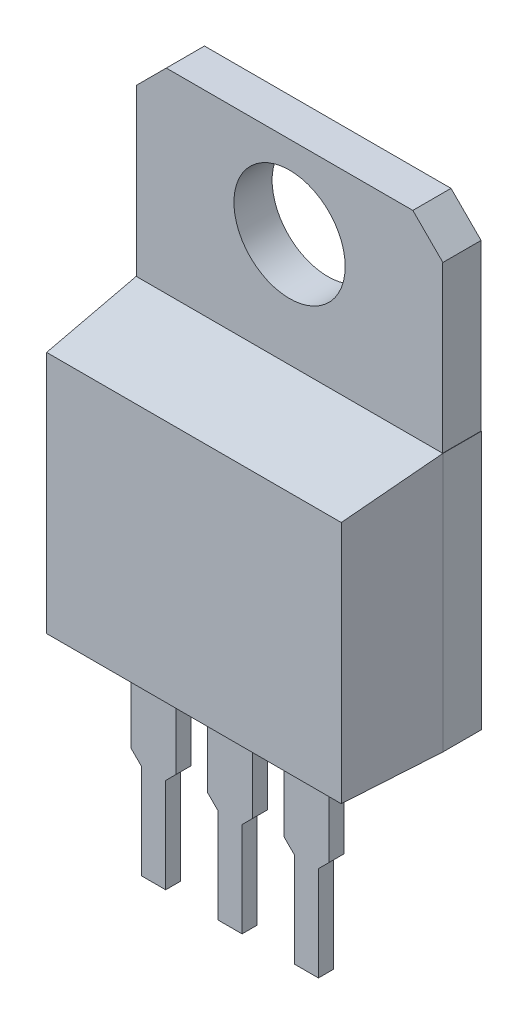
SolidWorks part; units mm, degrees
ref_plane "Plan de face" through (0, 0, 0) normal (0, 0, 1) x (1, 0, 0)
ref_plane "Plan de dessus" through (0, 0, 0) normal (0, 1, 0) x (1, 0, 0)
ref_plane "Plan de droite" through (0, 0, 0) normal (1, 0, 0) x (0, 0, -1)
sketch "Esquisse1" plane through (0, 0, 0) normal (0, 0, 1) x (1, 0, 0)
  line L0 (0, 15.1) -> (0, 12.36) construction
  line L1 (-5.1, 15.1) -> (5.1, 15.1)
  line L2 (-5.1, 15.1) -> (-5.1, 0)
  line L3 (-5.1, 0) -> (5.1, 0)
  line L4 (5.1, 15.1) -> (5.1, 0)
  line L5 (-5.1, 15.1) -> (5.1, 0) construction
  line L6 (-5.1, 0) -> (5.1, 15.1) construction
  circle A0 centre (0, 12.36) radius 1.85
  point P0 (0, 7.55)
  dimension "D4" = 3.7
  dimension "D1" = 15.1
  dimension "D2" = 10.2
  dimension "D3" = 2.74
extrude "Boss.-Extru.1" add sketch "Esquisse1" along normal blind 1.27
sketch "Esquisse2" plane through (0, 0, 1.27) normal (0, 0, 1) x (1, 0, 0)
  line L0 (5.1, 0) -> (5.1, 15.1) construction
  line L1 (-5.1, 0) -> (5.1, 0)
  line L2 (-5.1, 0) -> (-5.1, 8.6)
  line L3 (-5.1, 8.6) -> (5.1, 8.6)
  line L4 (5.1, 0) -> (5.1, 8.6)
  dimension "D1" = 8.6
extrude "Boss.-Extru.2" add sketch "Esquisse2" along normal blind 3.18
sketch "Esquisse3" plane through (0, 8.6, 0) normal (0, 1, 0) x (1, 0, 0)
  line L0 (5.1, -1.27) -> (4.9, -4.45)
  line L1 (5.1, -4.45) -> (-5.1, -4.45) construction
  line L2 (4.9, -4.45) -> (5.1, -4.45)
  line L3 (5.1, -4.45) -> (5.1, -1.27)
  line L4 (-5.1, -1.27) -> (-5.1, -4.45)
  line L5 (-5.1, -4.45) -> (-4.9, -4.45)
  line L6 (-4.9, -4.45) -> (-5.1, -1.27)
  dimension "D1" = 0.2
extrude "Enlèv. mat.-Extru.1" cut sketch "Esquisse3" against normal through all
sketch "Esquisse4" plane through (5.1, 0, 0) normal (1, 0, 0) x (0, 0, -1)
  line L0 (-1.27, 8.6) -> (-4.45, 8.1)
  line L1 (-4.45, 0) -> (-4.45, 8.6) construction
  line L2 (-4.45, 8.1) -> (-4.45, 8.6)
  line L3 (-4.45, 8.6) -> (-1.27, 8.6)
  dimension "D1" = 0.5
extrude "Enlèv. mat.-Extru.2" cut sketch "Esquisse4" against normal through all
sketch "Esquisse5" plane through (0, 0, 0) normal (0, -1, 0) x (1, 0, 0)
  line L0 (0, 0) -> (0, 3) construction
  line L1 (-0.75, 2.75) -> (0.75, 2.75)
  line L2 (-0.75, 2.75) -> (-0.75, 3.25)
  line L3 (-0.75, 3.25) -> (0.75, 3.25)
  line L4 (0.75, 2.75) -> (0.75, 3.25)
  line L5 (-0.75, 2.75) -> (0.75, 3.25) construction
  line L6 (-0.75, 3.25) -> (0.75, 2.75) construction
  line L7 (1.79, 2.75) -> (3.29, 2.75)
  line L8 (1.79, 2.75) -> (1.79, 3.25)
  line L9 (1.79, 3.25) -> (3.29, 3.25)
  line L10 (3.29, 2.75) -> (3.29, 3.25)
  line L11 (1.79, 2.75) -> (3.29, 3.25) construction
  line L12 (1.79, 3.25) -> (3.29, 2.75) construction
  line L13 (-1.79, 2.75) -> (-3.29, 2.75)
  line L14 (-1.79, 2.75) -> (-1.79, 3.25)
  line L15 (-1.79, 3.25) -> (-3.29, 3.25)
  line L16 (-3.29, 2.75) -> (-3.29, 3.25)
  line L17 (-1.79, 2.75) -> (-3.29, 3.25) construction
  line L18 (-1.79, 3.25) -> (-3.29, 2.75) construction
  line L19 (-5.1, 0) -> (5.1, 0) construction
  point P0 (0, 3)
  point P5 (2.54, 3)
  point P10 (-2.54, 3)
  dimension "D1" = 2.54
  dimension "D2" = 2.54
  dimension "D3" = 0.5
  dimension "D4" = 2.75
  dimension "D5" = 1.5
extrude "Boss.-Extru.3" add sketch "Esquisse5" along normal blind 3.1
sketch "Esquisse6" plane through (0, -3.1, 0) normal (0, -1, 0) x (1, 0, 0)
  line L0 (-1.79, 3.25) -> (-3.29, 3.25) construction
  line L1 (-2.94, 3.25) -> (-2.14, 3.25)
  line L2 (-2.94, 3.25) -> (-2.94, 2.75)
  line L3 (-2.94, 2.75) -> (-2.14, 2.75)
  line L4 (-2.14, 3.25) -> (-2.14, 2.75)
  line L5 (-3.29, 2.75) -> (-1.79, 2.75) construction
  line L6 (0.75, 3.25) -> (-0.75, 3.25) construction
  line L7 (-0.4, 3.25) -> (0.4, 3.25)
  line L8 (-0.4, 3.25) -> (-0.4, 2.75)
  line L9 (-0.4, 2.75) -> (0.4, 2.75)
  line L10 (0.4, 3.25) -> (0.4, 2.75)
  line L11 (-0.75, 2.75) -> (0.75, 2.75) construction
  line L12 (3.29, 3.25) -> (1.79, 3.25) construction
  line L13 (2.14, 3.25) -> (2.94, 3.25)
  line L14 (2.14, 3.25) -> (2.14, 2.75)
  line L15 (2.14, 2.75) -> (2.94, 2.75)
  line L16 (2.94, 3.25) -> (2.94, 2.75)
  line L17 (1.79, 2.75) -> (3.29, 2.75) construction
  line L18 (-3.29, 3) -> (-2.94, 3) construction
  line L19 (-3.29, 3.25) -> (-3.29, 2.75) construction
  line L20 (-2.14, 3) -> (-1.79, 3) construction
  line L21 (-1.79, 2.75) -> (-1.79, 3.25) construction
  line L22 (-0.75, 3) -> (-0.4, 3) construction
  line L23 (-0.75, 3.25) -> (-0.75, 2.75) construction
  line L24 (0.4, 3) -> (0.75, 3) construction
  line L25 (0.75, 2.75) -> (0.75, 3.25) construction
  line L26 (2.14, 3) -> (1.79, 3) construction
  line L27 (1.79, 3.25) -> (1.79, 2.75) construction
  line L28 (2.94, 3) -> (3.29, 3) construction
  line L29 (3.29, 2.75) -> (3.29, 3.25) construction
  dimension "D1" = 0.8
extrude "Boss.-Extru.4" add sketch "Esquisse6" along normal blind 3.5
chamfer "Chanfrein1" distance 0.35 angle 45 6 edges at (2.94, -3.1, 3) (0.4, -3.1, 3) (-2.14, -3.1, 3) (2.14, -3.1, 3) (-0.4, -3.1, 3) (-2.94, -3.1, 3)
chamfer "Chanfrein2" distance 1 angle 45 2 edges at (5.1, 15.1, 0.635) (-5.1, 15.1, 0.635)
sketch "Esquisse8" plane through (5.1, 0, 0) normal (1, 0, 0) x (0, 0, -1)
  line L1 (0, 14.1) -> (-1.27, 14.1)
  line L2 (0, 14.1) -> (0, 8.6)
  line L3 (0, 8.6) -> (-1.27, 8.6)
  line L4 (-1.27, 14.1) -> (-1.27, 8.6)
extrude "Enlèv. mat.-Extru.4" cut sketch "Esquisse8" against normal blind 0.01
sketch "Esquisse9" plane through (-5.1, 0, 0) normal (-1, 0, 0) x (0, 0, 1)
  line L1 (1.27, 8.6) -> (0, 8.6)
  line L2 (1.27, 8.6) -> (1.27, 14.1)
  line L3 (1.27, 14.1) -> (0, 14.1)
  line L4 (0, 8.6) -> (0, 14.1)
extrude "Enlèv. mat.-Extru.5" cut sketch "Esquisse9" against normal blind 0.01
sketch "Esquisse11" plane through (0, 0, 0) normal (0, 0, -1) x (-1, 0, 0)
  line L0 (-5.1, 0) -> (-5.1, 8.6)
  line L1 (-5.1, 8.6) -> (-3.6, 8.6)
  line L2 (-3.6, 8.6) -> (-3.6, 2)
  line L3 (-3.6, 2) -> (3.59, 2)
  line L4 (3.59, 2) -> (3.59, 8.6)
  line L5 (3.59, 8.6) -> (5.09, 8.6)
  line L6 (5.09, 8.6) -> (5.1, 0)
  line L7 (5.1, 0) -> (-5.1, 0)
  dimension "D1" = 1.5
  dimension "D2" = 1.5
  dimension "D3" = 2
extrude "Boss.-Extru.6" add sketch "Esquisse11" along normal blind 0.01
